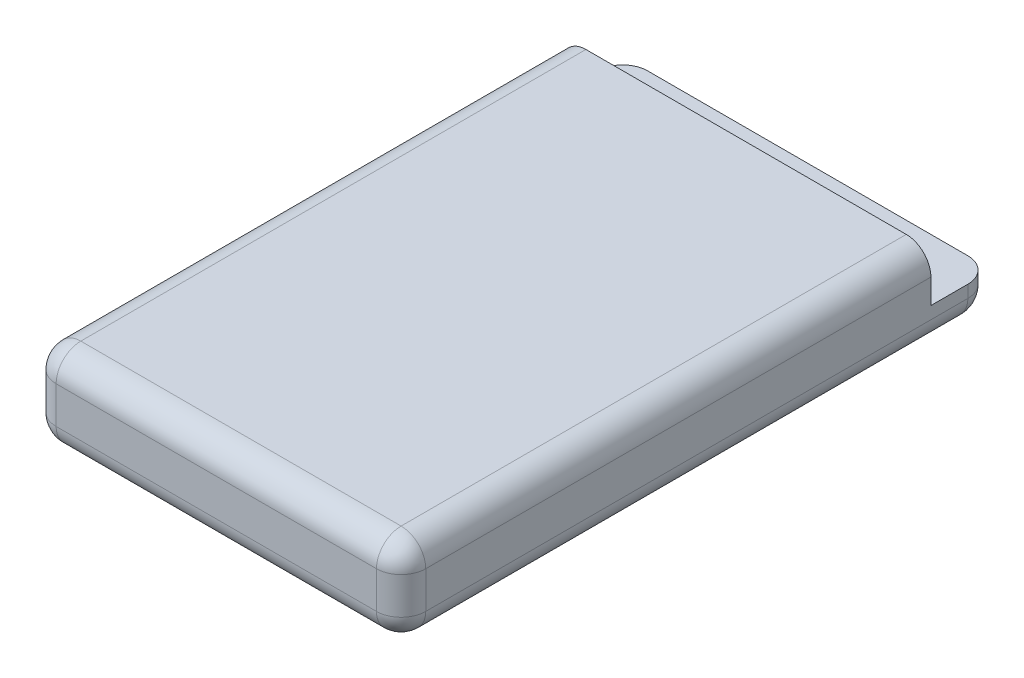
SolidWorks part; units mm, degrees
ref_plane "Спереди" through (0, 0, 0) normal (0, 0, 1) x (1, 0, 0)
ref_plane "Сверху" through (0, 0, 0) normal (0, 1, 0) x (1, 0, 0)
ref_plane "Справа" through (0, 0, 0) normal (1, 0, 0) x (0, 0, -1)
sketch "Эскиз1" plane through (0, 0, 0) normal (0, 1, 0) x (1, 0, 0)
  line L1 (-15, -24) -> (15, -24)
  line L2 (-15, -24) -> (-15, 24)
  line L3 (-15, 24) -> (15, 24)
  line L4 (15, -24) -> (15, 24)
  line L5 (-15, -24) -> (15, 24) construction
  line L6 (-15, 24) -> (15, -24) construction
  point P0 (0, 0)
  dimension "D1" = 48
  dimension "D2" = 30
extrude "Бобышка-Вытянуть1" add sketch "Эскиз1" along normal blind 7
fillet "Скругление1" radius 2 8 edges at (0, 0, -24) (-15, 0, 0) (0, 0, 24) (15, 0, 0) (0, 7, 24) (-15, 7, 0) (0, 7, -24) (15, 7, 0)
fillet "Скругление2" radius 2 12 edges at (14.4142, 6.4142, -23.4142) (14.4142, 0.5858, -23.4142) (14.4142, 6.4142, 23.4142) (14.4142, 0.5858, 23.4142) (-14.4142, 6.4142, -23.4142) (-14.4142, 0.5858, -23.4142) (-14.4142, 6.4142, 23.4142) (-14.4142, 0.5858, 23.4142) (15, 3.5, -24) (15, 3.5, 24) (-15, 3.5, -24) (-15, 3.5, 24)
sketch "Эскиз2" plane through (0, 7, 0) normal (0, 1, 0) x (1, 0, 0)
  line L1 (-15.5748, 24) -> (18.279, 24)
  line L2 (-15.5748, 24) -> (-15.5748, 19)
  line L3 (-15.5748, 19) -> (18.279, 19)
  line L4 (18.279, 24) -> (18.279, 19)
  line L5 (-13, 24) -> (13, 24) construction
  line L6 (-13, 24) -> (13, 24)
  line M5 (-13, 22) -> (-13, -22)
  line M7 (13, -22) -> (13, 22)
  line M8 (13, 22) -> (-13, 22)
  dimension "D1" = 5
extrude "Вырез-Вытянуть1" cut sketch "Эскиз2" against normal blind 4 contours L3 M5 M7 M8 | L4 L1 L2 L3 M5 M8 M7 region at (2.5076, 7, -22.3546) region at (0, 7, -20.5)
ref_plane "Плоскость1" through (13, -4.5, 1.1353) normal (0, 0, -1) x (-1, 0, 0)
sketch "Эскиз5" plane through (0, -4.5, 0) normal (0, -1, 0) x (1, 0, 0)
  line L0 (4.578, -4.5831) -> (4.578, -15.6614)
  line L1 (1, -4.5831) -> (-13, -4.5831) construction
  line L2 (4.578, -15.6614) -> (-13, -15.6614)
  line L3 (-13, 22) -> (-13, -22) construction
  line L4 (-13, -15.6614) -> (-13, -7.7638)
  line L5 (-13, -7.7638) -> (1.1861, -7.7638)
  line L6 (1.1861, -7.7638) -> (1.1861, -4.5831)
  line L7 (1.1861, -4.5831) -> (4.578, -4.5831)
